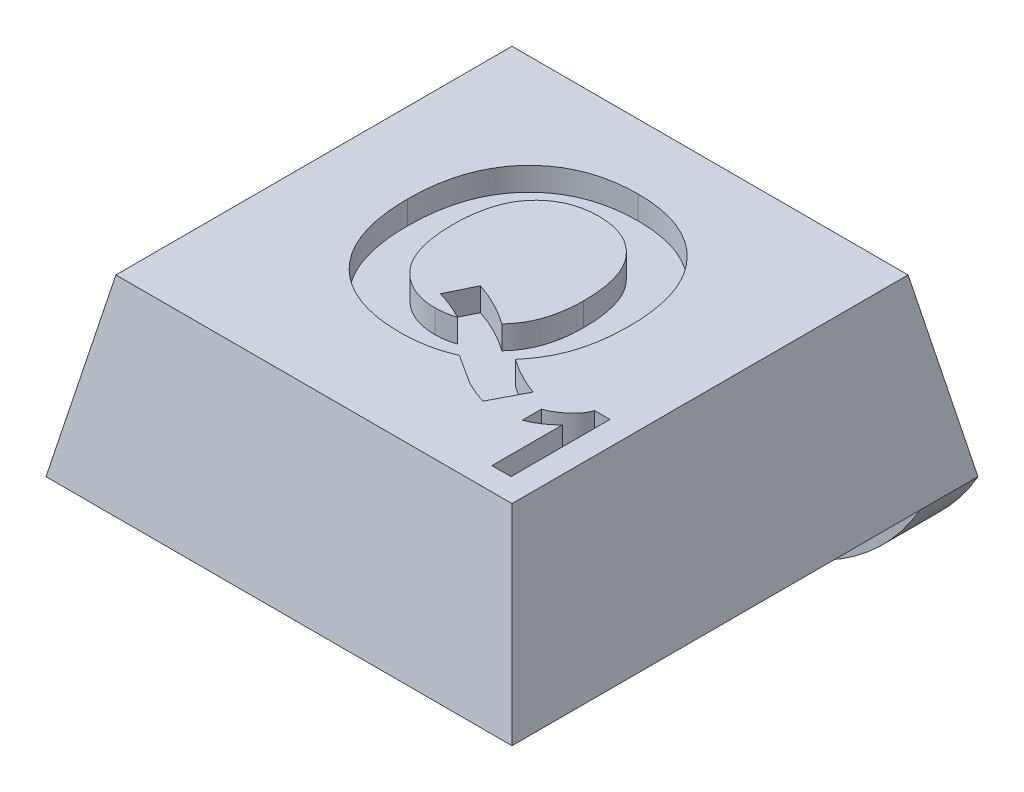
SolidWorks part; units mm, degrees
ref_plane "Front Plane" through (0, 0, 0) normal (0, 0, 1) x (1, 0, 0)
ref_plane "Top Plane" through (0, 0, 0) normal (0, 1, 0) x (1, 0, 0)
ref_plane "Right Plane" through (0, 0, 0) normal (1, 0, 0) x (0, 0, -1)
sketch "Sketch1" plane through (0, 0, 0) normal (0, 1, 0) x (1, 0, 0)
  line L1 (0, 0) -> (8, 0)
  line L2 (0, 0) -> (0, 8)
  line L3 (0, 8) -> (8, 8)
  line L4 (8, 0) -> (8, 8)
  dimension "D1" = 8
  dimension "D2" = 8
extrude "Boss-Extrude1" add sketch "Sketch1" along normal blind 3
sketch "Sketch2" plane through (0, 0, 0) normal (0, 0, 1) x (1, 0, 0)
  line L0 (0, 0) -> (0.6, 3)
  line L1 (0, 3) -> (8, 3) construction
  line L2 (0.6, 3) -> (0, 3)
  line L3 (0, 3) -> (0, 0)
  line L4 (8, 0) -> (7.4, 3)
  line L5 (7.4, 3) -> (8, 3)
  line L6 (8, 3) -> (8, 0)
  dimension "D1" = 0.6
  dimension "D2" = 0.6
extrude "Cut-Extrude1" cut sketch "Sketch2" against normal through all both and the other way through all
sketch "Sketch3" plane through (0, 0, 0) normal (1, 0, 0) x (0, 0, -1)
  line L0 (0, 0) -> (0.6, 3)
  line L1 (8, 3) -> (0, 3) construction
  line L2 (0.6, 3) -> (0, 3)
  line L3 (0, 3) -> (0, 0)
  line L4 (8, 3) -> (7.4, 3)
  line L5 (7.4, 3) -> (8, 0)
  line L6 (8, 3) -> (8, 0)
  dimension "D1" = 0.6
  dimension "D2" = 0.6
extrude "Cut-Extrude2" cut sketch "Sketch3" along normal blind 11
sketch "Sketch4" plane through (0, 0, 0) normal (0, -1, 0) x (1, 0, 0)
  line L0 (8, 0) -> (8, -8) construction
  line L3 (0, 0) -> (8, 0) construction
  circle A0 centre (4, -3.75) radius 1.75
  dimension "D1" = 3.5
  dimension "D2" = 4
  dimension "D3" = 3.75
extrude "Cut-Extrude3" cut sketch "Sketch4" against normal blind 0.4
sketch "Sketch5" plane through (0, 0, 0) normal (0, -1, 0) x (1, 0, 0)
  line L0 (8, 0) -> (8, -8) construction
  line L1 (0, -8) -> (8, -8)
  line L2 (0, -8) -> (0, -7)
  line L3 (0, -7) -> (8, -7)
  line L4 (8, -8) -> (8, -7)
  dimension "D1" = 1
extrude "Boss-Extrude2" add sketch "Sketch5" along normal blind 2
fillet "Fillet1" radius 4 2 edges at (8, -2, -7.5) (0, -2, -7.5)
sketch "Sketch6" plane through (0, 3, 0) normal (0, 1, 0) x (1, 0, 0)
  text T0 "Q" font "Arial" height 4
extrude "Cut-Extrude4" cut sketch "Sketch6" against normal blind 0.4
sketch "Sketch7" plane through (0, 3, 0) normal (0, 1, 0) x (1, 0, 0)
  text T0 "1" font "Arial" height 1.7
extrude "Cut-Extrude5" cut sketch "Sketch7" against normal blind 0.5
